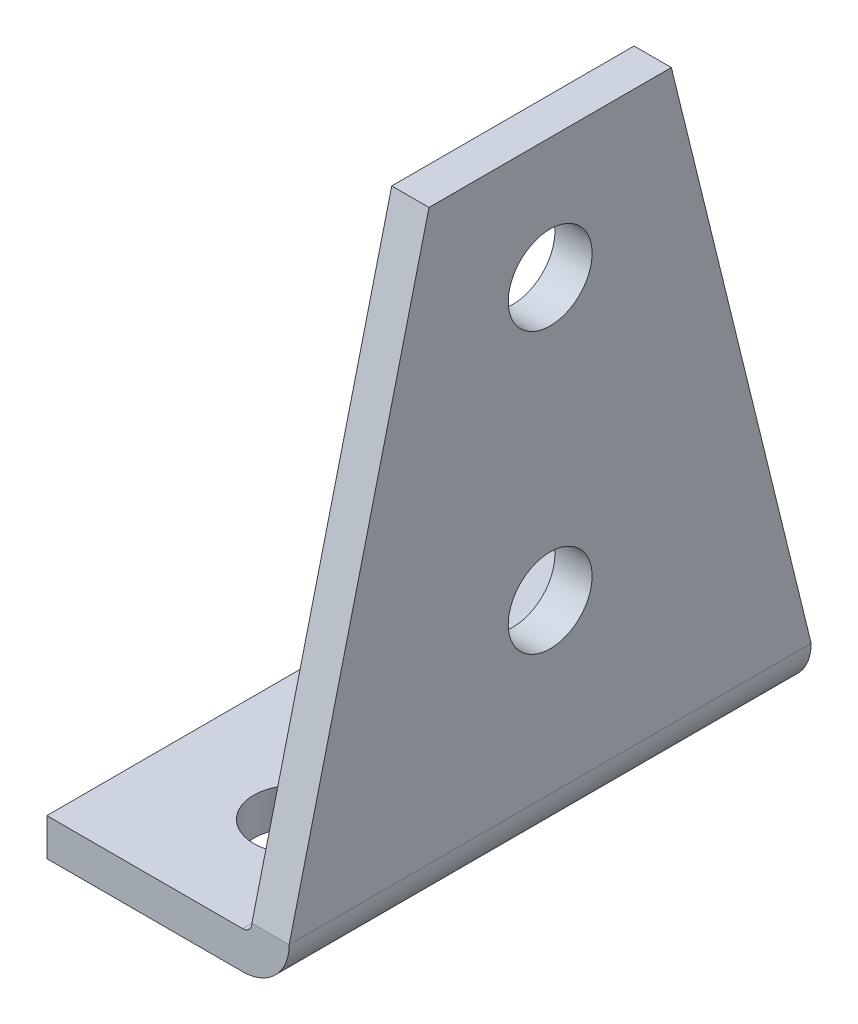
SolidWorks part; units mm, degrees
ref_plane "Front Plane" through (0, 0, 0) normal (0, 0, 1) x (1, 0, 0)
ref_plane "Top Plane" through (0, 0, 0) normal (0, 1, 0) x (1, 0, 0)
ref_plane "Right Plane" through (0, 0, 0) normal (1, 0, 0) x (0, 0, -1)
sketch "Sketch1" plane through (0, 0, 0) normal (0, 0, 1) x (1, 0, 0)
  line L0 (-41.275, 0) -> (-7.9375, 0)
  line L1 (0, 7.9375) -> (0, 104.775)
  arc A0 (-7.9375, 0) -> (0, 7.9375) centre (-7.9375, 7.9375) ccw
  point P6 (0, 0)
  dimension "D3" = 7.9375
  dimension "D1" = 41.275
  dimension "A" = 104.775
extrude "Extrude-Thin1" add sketch "Sketch1" along normal mid plane 88.9 thin thin type one direction reverse wall 6.35
sketch "Sketch2" plane through (-6.35, 0, 0) normal (-1, 0, 0) x (0, 0, 1)
  line L0 (-44.45, 7.9375) -> (-20.6375, 104.775)
  line L1 (44.45, 104.775) -> (-44.45, 104.775) construction
  line L2 (20.6375, 104.775) -> (44.45, 7.9375)
  line L3 (-20.6375, 104.775) -> (20.6375, 104.775)
  line L4 (0, 0) -> (0, 104.775) construction
  dimension "D1" = 41.275
extrude "Cut-Extrude2" cut sketch "Sketch2" against normal through all and the other way through all
sketch "Sketch3" plane through (-6.35, 0, 0) normal (-1, 0, 0) x (0, 0, 1)
  line L0 (20.6375, 104.775) -> (-20.6375, 104.775) construction
  circle A0 centre (0, 84.1375) radius 7.1438
  circle A1 centre (0, 36.5125) radius 7.1438
  dimension "Hole Size" = 14.2875
  dimension "edge" = 20.6375
  dimension "D1" = 47.625
extrude "Cut-Extrude3" cut sketch "Sketch3" against normal through all
sketch "Sketch4" plane through (0, 6.35, 0) normal (0, 1, 0) x (1, 0, 0)
  line L0 (-41.275, 44.45) -> (-7.9375, 44.45) construction
  line L1 (-41.275, -44.45) -> (-7.9375, -44.45) construction
  line L5 (-41.275, -44.45) -> (-41.275, 44.45) construction
  line L6 (0, 20.6375) -> (0, 44.45) construction
  circle A0 centre (-19.5263, 23.8125) radius 7.1438
  circle A1 centre (-19.5263, -23.8125) radius 7.1438
  dimension "D1" = 14.2875
  dimension "D2" = 20.6375
  dimension "D3" = 20.6375
  dimension "D4" = 14.605
  dimension "D5" = 19.5263
  dimension "D6" = 21.7488
extrude "Cut-Extrude4" cut sketch "Sketch4" against normal through all
equation "\"D1@Sketch4\" = \"Hole Size@Sketch3\""
equation "\"D2@Sketch4\" = \"edge@Sketch3\""
equation "\"D3@Sketch4\" = \"D2@Sketch4\""
